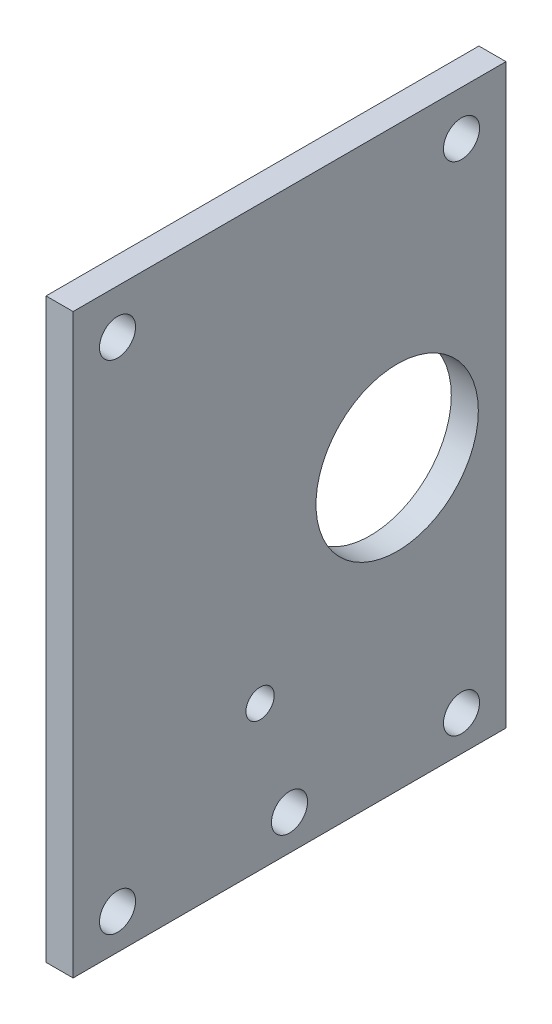
SolidWorks part; units mm, degrees
material "6061 Alloy"
ref_plane "Front Plane" through (0, 0, 0) normal (0, 0, 1) x (1, 0, 0)
ref_plane "Top Plane" through (0, 0, 0) normal (0, 1, 0) x (1, 0, 0)
ref_plane "Right Plane" through (0, 0, 0) normal (1, 0, 0) x (0, 0, -1)
sketch "Sketch2" plane through (0, 0, 0) normal (1, 0, 0) x (0, 0, -1)
  line L1 (-38.1, -50.8) -> (38.1, -50.8)
  line L2 (-38.1, -50.8) -> (-38.1, 50.8)
  line L3 (-38.1, 50.8) -> (38.1, 50.8)
  line L4 (38.1, -50.8) -> (38.1, 50.8)
  line L5 (-38.1, -50.8) -> (38.1, 50.8) construction
  line L6 (-38.1, 50.8) -> (38.1, -50.8) construction
  point P0 (0, 0)
  dimension "D1" = 76.2
  dimension "D2" = 101.6
extrude "Boss-Extrude1" add sketch "Sketch2" along normal blind 4.7625
sketch "Sketch3" plane through (4.7625, 0, 0) normal (1, 0, 0) x (0, 0, -1)
  line L5 (30.2768, -44.5643) -> (-30.2768, -44.5643) construction
  line L6 (-30.2768, 42.9768) -> (30.2768, 42.9768) construction
  line L7 (30.2768, 42.9768) -> (30.2768, -44.5643) construction
  line L8 (-30.2768, 42.9768) -> (-30.2768, -44.5643) construction
  line L9 (-38.1, 50.8) -> (-38.1, -50.8) construction
  line L10 (38.1, 50.8) -> (-38.1, 50.8) construction
  line L11 (38.1, -50.8) -> (38.1, 50.8) construction
  line L12 (-38.1, -50.8) -> (38.1, -50.8) construction
  circle A0 centre (30.2768, -44.5643) radius 3.175
  circle A1 centre (30.2768, 42.9768) radius 3.175
  circle A2 centre (-30.2768, 42.9768) radius 3.175
  circle A3 centre (-30.2768, -44.5643) radius 3.175
  circle A4 centre (18.9484, 0) radius 14.2875
  circle A5 centre (-5.1816, -25.4) radius 2.4892
  circle A6 centre (0, -44.5643) radius 3.175
  dimension "D1" = 6.35
  dimension "D5" = 7.8232
  dimension "D7" = 7.8232
  dimension "D8" = 6.2357
  dimension "D9" = 28.575
  dimension "D10" = 50.8
  dimension "D11" = 4.9784
  dimension "D12" = 25.4
  dimension "D6" = 7.8232
  dimension "D13" = 24.13
  dimension "D14" = 19.1516
extrude "Cut-Extrude1" cut sketch "Sketch3" against normal blind 6.35 contours A1
extrude "Cut-Extrude2" cut sketch "Sketch3<4>" against normal blind 6.35
sketch "Sketch3<4>" plane through (4.7625, 0, 0) normal (1, 0, 0) x (0, 0, -1) same geometry as "Sketch3"
